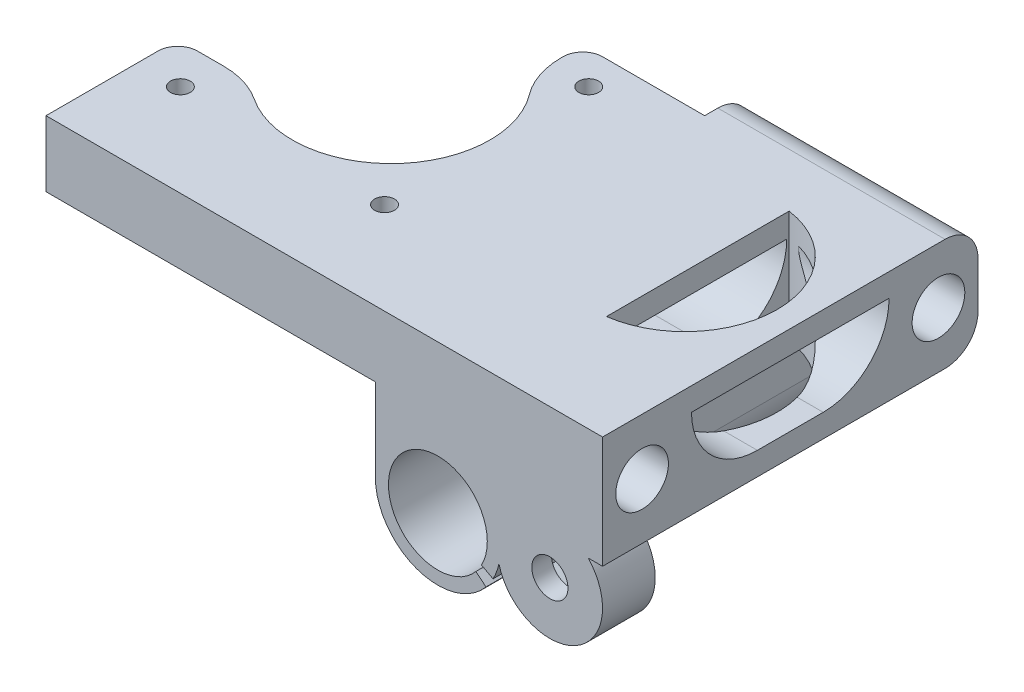
SolidWorks part; units mm, degrees
material "ABS generico"
ref_plane "Front Plane" through (0, 0, 0) normal (0, 0, 1) x (1, 0, 0)
ref_plane "Top Plane" through (0, 0, 0) normal (0, 1, 0) x (1, 0, 0)
ref_plane "Right Plane" through (0, 0, 0) normal (1, 0, 0) x (0, 0, -1)
sketch "Sketch1" plane through (0, 0, 0) normal (0, 0, 1) x (1, 0, 0)
  line L0 (73.5, -17) -> (73.5, 0)
  line L1 (43.3893, -17) -> (39, -17)
  line L2 (39, -17) -> (39, -22.5) construction
  line L3 (65.5, -18.2276) -> (61.8, -20.3638) construction
  line L4 (61.8, -20.3638) -> (61.8, -24.6362) construction
  line L7 (73.5, -17) -> (53.6024, -17)
  line L8 (61.8, -24.6362) -> (65.5, -26.7724) construction
  line L10 (39, 0) -> (73.5, 0)
  line L11 (57.9584, -23.294) -> (57.9584, -17) construction
  line L12 (65.5, -26.7724) -> (69.2, -24.6362) construction
  line L13 (69.2, -24.6362) -> (69.2, -20.3638) construction
  line L14 (54.2695, -27.2923) -> (55.8016, -28.5649) construction
  line L15 (39, -17) -> (39, 0)
  line L16 (56.8764, -26.9641) -> (55.1187, -26.0274) construction
  line L17 (69.2, -20.3638) -> (65.5, -18.2276) construction
  circle A0 centre (65.5, -22.5) radius 3.7 construction
  arc A1 (57.7674, -24.5509) -> (71.3095, -17) centre (65.5, -22.5) ccw construction
  arc A2 (43.3893, -17) -> (53.6024, -17) centre (48.4959, -22.4988) ccw construction
  circle A3 centre (65.5, -22.5) radius 2.75 construction
  arc A4 (55.8016, -28.5649) -> (39, -22.5) centre (48.4959, -22.4988) cw construction
  arc A6 (57.9584, -23.294) -> (56.8764, -26.9641) centre (48.4959, -22.4988) cw construction
  arc A7 (43.3893, -17) -> (53.6024, -17) centre (48.4959, -22.4988) cw
  dimension "D2" = 5.5
  dimension "D3" = 34.5
  dimension "D1" = 7.4
  dimension "D4" = 17
extrude "Extrude1" add sketch "Sketch1" against normal blind 57
sketch "Sketch2" plane through (0, 0, 0) normal (0, 0, 1) x (1, 0, 0)
  line L0 (57.9584, -23.294) -> (57.9584, -17) construction
  line L1 (73.5, -17) -> (53.6024, -17) construction
  line L2 (57.9584, -23.294) -> (57.9584, -17)
  line L3 (71.3095, -17) -> (57.9584, -17)
  arc A1 (56.8764, -26.9641) -> (57.9584, -23.294) centre (48.4959, -22.4988) ccw construction
  arc A2 (57.7674, -24.5509) -> (71.3095, -17) centre (65.5, -22.5) ccw construction
  circle A3 centre (65.5, -22.5) radius 2.75 construction
  arc A4 (57.7674, -24.5509) -> (57.9584, -23.294) centre (48.4959, -22.4988) ccw
  arc A5 (57.7674, -24.5509) -> (71.3095, -17) centre (65.5, -22.5) ccw
  circle A6 centre (65.5, -22.5) radius 2.75
extrude "Extrude2" add sketch "Sketch2" against normal blind 8
sketch "Sketch3" plane through (0, 0, -8) normal (0, 0, -1) x (-1, 0, 0)
  line L6 (-69.5, -20.1906) -> (-65.5, -17.8812)
  line L7 (-65.5, -17.8812) -> (-61.5, -20.1906)
  line L8 (-61.5, -20.1906) -> (-61.5, -24.8094)
  line L9 (-61.5, -24.8094) -> (-65.5, -27.1188)
  line L10 (-65.5, -27.1188) -> (-69.5, -24.8094)
  line L11 (-69.5, -24.8094) -> (-69.5, -20.1906)
extrude "Extrude3" cut sketch "Sketch3" against normal blind 5
sketch "Sketch4" plane through (0, 0, 0) normal (0, 0, 1) x (1, 0, 0)
  line L0 (39, -17) -> (39, -22.5) construction
  line L1 (43.3893, -17) -> (39, -17) construction
  line L2 (56.8764, -26.9641) -> (55.1187, -26.0274) construction
  line L3 (54.2695, -27.2923) -> (55.8016, -28.5649) construction
  line L4 (57.9584, -23.294) -> (57.9584, -17) construction
  line L5 (73.5, -17) -> (53.6024, -17) construction
  line L6 (39, -17) -> (39, -22.5)
  line L7 (43.3893, -17) -> (39, -17)
  line L8 (56.8764, -26.9641) -> (55.1187, -26.0274)
  line L9 (54.2695, -27.2923) -> (55.8016, -28.5649)
  line L10 (57.9584, -23.294) -> (57.9584, -17)
  line L11 (57.9584, -17) -> (53.6024, -17)
  arc A0 (43.3893, -17) -> (53.6024, -17) centre (48.4959, -22.4988) ccw construction
  arc A1 (56.8764, -26.9641) -> (57.9584, -23.294) centre (48.4959, -22.4988) ccw construction
  arc A2 (39, -22.5) -> (55.8016, -28.5649) centre (48.4959, -22.4988) ccw construction
  arc A3 (43.3893, -17) -> (54.2695, -27.2923) centre (48.4959, -22.4988) ccw
  arc A4 (56.8764, -26.9641) -> (57.9584, -23.294) centre (48.4959, -22.4988) ccw
  arc A5 (39, -22.5) -> (55.8016, -28.5649) centre (48.4959, -22.4988) ccw
  arc A6 (55.1187, -26.0274) -> (53.6024, -17) centre (48.4959, -22.4988) ccw
extrude "Extrude4" add sketch "Sketch4" against normal blind 50
sketch "Sketch5" plane through (73.5, 0, 0) normal (1, 0, 0) x (0, 0, -1)
  line L0 (0, -8.5) -> (57, -8.5) construction
  line L1 (0, -17) -> (0, 0) construction
  line L2 (57, -17) -> (57, 0) construction
  line L3 (28.5, 0) -> (28.5, -17) construction
  line L4 (57, 0) -> (0, 0) construction
  line L5 (57, -17) -> (0, -17) construction
  line L7 (13.5, -13.5) -> (43.5, -13.5)
  line L8 (13.5, -13.5) -> (13.5, -3.5)
  line L9 (13.5, -3.5) -> (43.5, -3.5)
  line L10 (43.5, -13.5) -> (43.5, -3.5)
  line L11 (13.5, -13.5) -> (43.5, -3.5) construction
  line L12 (13.5, -3.5) -> (43.5, -13.5) construction
  circle A0 centre (6, -8.5) radius 4
  circle A1 centre (51, -8.5) radius 4
  point P12 (28.5, -8.5)
  dimension "D4" = 8
  dimension "D1" = 10
  dimension "D2" = 30
  dimension "D3" = 22.5
extrude "Extrude5" cut sketch "Sketch5" against normal blind 33 contours A0 | A1
sketch "Sketch6" plane through (73.5, 0, 0) normal (1, 0, 0) x (0, 0, -1)
  line L0 (13.5, -13.5) -> (13.5, -3.5) construction
  line L1 (13.5, -3.5) -> (43.5, -3.5) construction
  line L2 (43.5, -13.5) -> (43.5, -3.5) construction
  line L3 (13.5, -13.5) -> (43.5, -13.5) construction
  line L4 (13.5, -13.5) -> (13.5, -3.5)
  line L5 (13.5, -3.5) -> (43.5, -3.5)
  line L6 (43.5, -13.5) -> (43.5, -3.5)
  line L7 (13.5, -13.5) -> (43.5, -13.5)
extrude "Extrude6" cut sketch "Sketch6" against normal blind 33
sketch "Sketch7" plane through (39, 0, 0) normal (-1, 0, 0) x (0, 0, 1)
  line L0 (0, -17) -> (0, 0) construction
  line L4 (0, 0) -> (0, -10)
  line L6 (-50, 0) -> (-50, -10)
  line L8 (-50, -10) -> (0, -10)
  line L11 (-50, 0) -> (0, 0)
extrude "Extrude7" add sketch "Sketch7" along normal blind 50
sketch "Sketch10" plane through (0, -10, 0) normal (0, -1, 0) x (1, 0, 0)
  line L0 (26.4008, 4.2075) -> (26.4008, -61.311) construction
  line L2 (-4.5992, 4.2075) -> (-4.5992, -61.311) construction
  line L3 (-23.5897, 0) -> (85.8099, 0) construction
  line L4 (-23.5897, -14) -> (85.8099, -14) construction
  line L5 (-23.5897, -45) -> (85.8099, -45) construction
  circle A0 centre (-4.5992, -45) radius 1.5
  circle A1 centre (26.4008, -45) radius 1.5
  circle A2 centre (26.4008, -14) radius 1.5
  circle A3 centre (-4.5992, -14) radius 1.5
  dimension "D4" = 3
  dimension "D1" = 31
  dimension "D2" = 14
  dimension "D3" = 31
  dimension "D5" = 2
  dimension "D6" = 2
extrude "Extrude10" cut sketch "Sketch10" against normal up to surface (10 mm away) up to face at (29.6667, 0, -36.25)
sketch "Sketch11" plane through (0, -10, 0) normal (0, -1, 0) x (1, 0, 0)
  circle A0 centre (-4.5992, -14) radius 2.75
  circle A1 centre (26.4008, -14) radius 2.75
  circle A2 centre (26.4008, -45) radius 2.75
  circle A4 centre (-4.5992, -45) radius 2.75 [skipped]
  dimension "D1" = 5.5
  dimension "D2" = 2
  dimension "D3" = 2
extrude "Extrude13" cut sketch "Sketch11" against normal blind 1
sketch "Sketch12" plane through (0, -10, 0) normal (0, -1, 0) x (1, 0, 0)
  line L1 (-4.5992, -14) -> (26.4008, -14) construction
  line L2 (-4.5992, -14) -> (-4.5992, -45) construction
  line L3 (-4.5992, -45) -> (26.4008, -45) construction
  line L4 (26.4008, -14) -> (26.4008, -45) construction
  circle A0 centre (10.9008, -30.5) radius 15
  dimension "D1" = 30
extrude "Extrude14" cut sketch "Sketch12" against normal up to surface (10 mm away) up to face at (-4.5992, 0, -12.5)
fillet "Fillet2" radius 5 3 edges at (41.1947, -17, -57) (63.5512, -17, -57) (48.4959, -14.9946, -57)
fillet "Fillet3" radius 5 1 edges at (56.25, 0, -57)
fillet "Fillet4" radius 10 1 edges at (57, -13.5, -43.5)
sketch "Sketch13" plane through (0, -17, 0) normal (0, -1, 0) x (1, 0, 0)
  line L1 (57.9584, -16.1375) -> (57.9584, -43.8625)
  line L2 (57.9584, -50) -> (57.9584, -8) construction
  arc A0 (57.9584, -43.8625) -> (57.9584, -16.1375) centre (55.9998, -30) ccw
extrude "Extrude15" cut sketch "Sketch13" against normal up to surface (17 mm away) up to face at (10.9008, 0, -15.5)
sketch "Sketch14" plane through (40.5, 0, 0) normal (1, 0, 0) x (0, 0, -1)
  line L4 (40, -3.5) -> (20, -3.5)
  line L5 (40, -3.5) -> (40, -13.5)
  line L6 (40, -13.5) -> (20, -13.5)
  line L7 (20, -3.5) -> (20, -13.5)
  point P1 (30, -8.5)
  dimension "D1" = 20
extrude "Extrude16" cut sketch "Sketch14" against normal blind 60
sketch "Sketch15" plane through (0, 0, 0) normal (0, 1, 0) x (1, 0, 0)
  line L0 (2.1139, 20) -> (-12.4389, 20)
  line L1 (-12.4389, 50) -> (20.4964, 50)
  line L2 (2.1139, 40) -> (2.1139, 20)
  line L3 (-12.4389, 20) -> (-12.4389, 50)
  line L5 (20.4964, 40) -> (20.4964, 50)
  line L6 (2.1139, 40) -> (20.4964, 40)
extrude "Extrude18" cut sketch "Sketch15" against normal blind 60
fillet "Fillet5" radius 10 1 edges at (57, -13.5, -13.5)
fillet "Fillet6" radius 12 4 edges at (0.1887, -5, -20) (22.509, -6.75, -40) (20.4964, -5, -42.0293)
fillet "Fillet7" radius 3 2 edges
fillet "Fillet8" radius 3 1 edges at (-11, -5, -20)
fillet "Fillet9" radius 3 1 edges at (20.4964, -5, -50)
